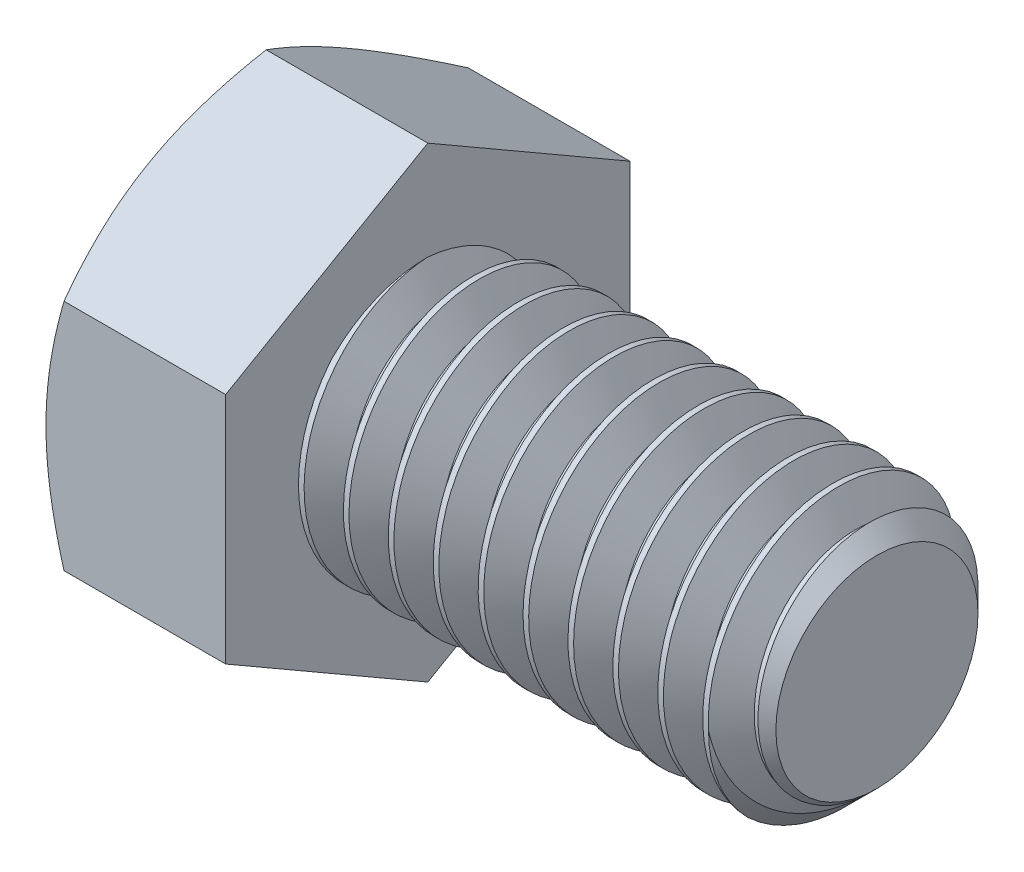
SolidWorks part; units mm, degrees
ref_plane "Front Plane" through (0, 0, 0) normal (0, 0, 1) x (1, 0, 0)
ref_plane "Top Plane" through (0, 0, 0) normal (0, 1, 0) x (1, 0, 0)
ref_plane "Right Plane" through (0, 0, 0) normal (1, 0, 0) x (0, 0, -1)
sketch "Sketch1" plane through (0, 0, 0) normal (0, 0, 1) x (1, 0, 0)
  line L0 (-11.1125, 0) -> (11.1125, 0) construction
  line L1 (11.1125, 4.7625) -> (11.1125, -4.7625) construction
  line L2 (-4.7625, 7.1438) -> (-4.7625, -7.1438) construction
  line L3 (-11.1125, 7.1437) -> (-11.1125, -7.1437) construction
  point P9 (-4.7625, 0)
  point P10 (5.5563, -4.7625)
  dimension "D1" = 5.5562
  dimension "Screw Dia" = 9.525
  dimension "Hex" = 14.2875
  dimension "Head Ht" = 6.35
  dimension "Screw Lenght" = 15.875
ref_plane "Plane2" through (11.1125, 0, 0) normal (1, 0, 0) x (0, 0, -1)
sketch "Sketch5" plane through (11.1125, 0, 0) normal (1, 0, 0) x (0, 0, -1)
  circle A0 centre (0, 0) radius 4.7625
extrude "Boss-Extrude3" add sketch "Sketch5" against normal up to vertex (15.875 mm away) up to point (-4.7625, 0, 0)
sketch "Sketch9" plane through (11.1125, 0, 0) normal (1, 0, 0) x (0, 0, -1)
  circle A1 centre (0, 0) radius 4.7625
  circle A2 centre (0, 0) radius 4.7625
  dimension "D1" = 0
curve "Helix/Spiral1" pitch 1.5875 height 17.4625 turns 11 parameters "Pitch"=1.5875
chamfer "Chamfer1" distance 1.1906 angle 45 1 edges at (11.1125, 0, -4.7625)
sketch "Sketch10" plane through (0, 0, 0) normal (0, 0, 1) x (1, 0, 0)
  line L0 (11.1125, 4.7625) -> (11.7078, 3.7314)
  line L1 (11.7078, 3.7314) -> (11.9063, 3.7314)
  line L2 (11.9063, 3.7314) -> (12.5016, 4.7625)
  line L3 (11.1125, 4.7625) -> (12.5016, 4.7625)
  line L4 (11.807, 4.7625) -> (11.807, 3.7314) construction
  line L5 (11.4102, 4.2469) -> (12.2039, 4.2469) construction
  dimension "D1" = 60
  dimension "D2" = 0.1984
  dimension "D3" = 0.7937
sweep "Cut-Sweep1" cut profiles "Sketch10" path "Helix/Spiral1"
sketch "Sketch11" plane through (0, 0, 0) normal (0, 0, 1) x (1, 0, 0)
  line L0 (-4.7625, 4.7625) -> (-4.7625, 0)
  line L1 (-4.7625, 0) -> (-15.875, 0)
  line L3 (-15.875, 0) -> (-20.6375, 4.7625)
  line L4 (-4.7625, 4.7625) -> (-20.6375, 4.7625)
  dimension "D1" = 45
  dimension "MIn Thread" = 31.75
revolve "Revolve1" [suppressed] add sketch "Sketch11" angle 360 about L1
sketch "Sketch6" plane through (-4.7625, 0, 0) normal (-1, 0, 0) x (0, 0, 1)
  line L0 (0, 7.1438) -> (0, -7.1438) construction
  line L1 (7.1437, 4.1244) -> (0, 8.2489)
  line L2 (0, 8.2489) -> (-7.1438, 4.1244)
  line L3 (-7.1438, 4.1244) -> (-7.1438, -4.1244)
  line L4 (-7.1438, -4.1244) -> (0, -8.2489)
  line L5 (0, -8.2489) -> (7.1438, -4.1244)
  line L6 (7.1438, -4.1244) -> (7.1437, 4.1244)
  circle A0 centre (0, 0) radius 7.1438 construction
extrude "Boss-Extrude4" add sketch "Sketch6" along normal up to vertex (6.35 mm away) up to point (-11.1125, -7.1437, 0)
sketch "Sketch7" plane through (-11.1125, 0, 0) normal (-1, 0, 0) x (0, 0, 1)
  circle A0 centre (0, 0) radius 7.1438 construction
  circle A1 centre (0, 0) radius 7.1438
sketch "Sketch8" plane through (-11.1125, 0, 0) normal (-1, 0, 0) x (0, 0, 1)
  circle A0 centre (0, 0) radius 7.1438 construction
  circle A1 centre (0, 0) radius 7.1438
extrude "Cut-Extrude3" cut sketch "Sketch8" against normal through all draft 60 flip side to cut
equation "\"D2@Sketch10\" = \"Pitch@Helix/Spiral1\"*.125"
equation "\"D3@Sketch10\" = \"Pitch@Helix/Spiral1\"*.5"
equation "\"D3@Helix/Spiral1\" = \"Screw Lenght@Sketch1\"+\"Pitch@Helix/Spiral1\""
equation "\"D1@Chamfer1\" = \"Pitch@Helix/Spiral1\"*.75"
equation "\"D1@Sketch1\" = \"Pitch@Helix/Spiral1\"*3.5"
